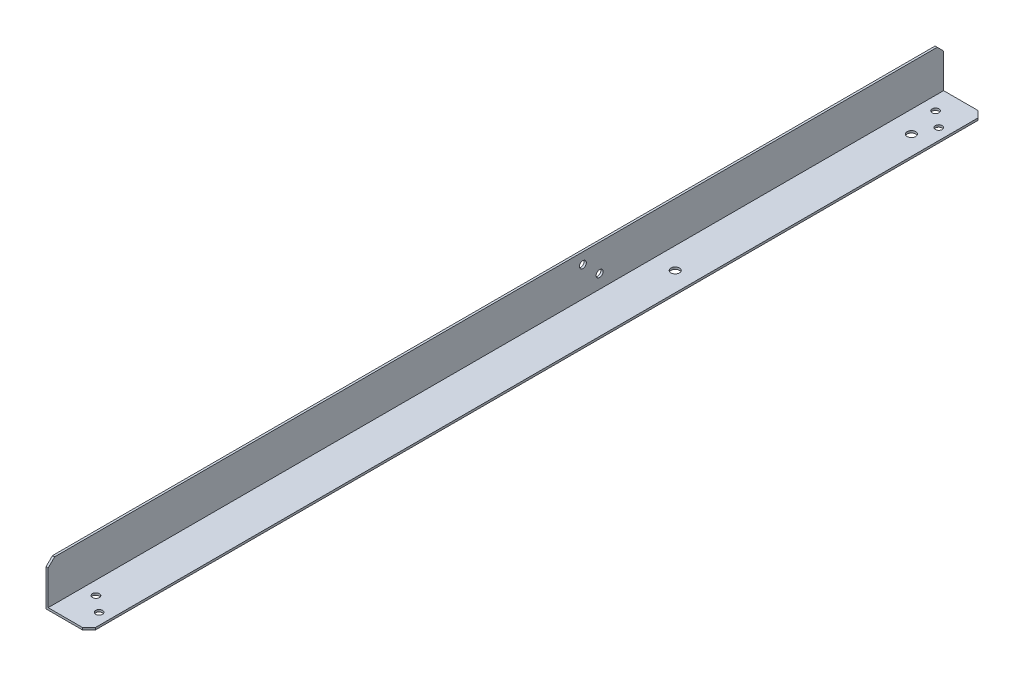
SolidWorks part; units mm, degrees
material "6063-T5"
ref_plane "Спереди" through (0, 0, 0) normal (0, 0, 1) x (1, 0, 0)
ref_plane "Сверху" through (0, 0, 0) normal (0, 1, 0) x (1, 0, 0)
ref_plane "Справа" through (0, 0, 0) normal (1, 0, 0) x (0, 0, -1)
sketch "Sketch1" plane through (0, 0, 0) normal (0, 0, 1) x (1, 0, 0)
  line L0 (0, 0) -> (20, 0)
  line L1 (20, 0) -> (20, 1)
  line L2 (20, 1) -> (1, 1)
  line L3 (1, 1) -> (1, 20)
  line L4 (1, 20) -> (0, 20)
  line L5 (0, 20) -> (0, 0)
  dimension "D1" = 20
  dimension "D2" = 20
  dimension "D4" = 1
extrude "Base" add sketch "Sketch1" along normal blind 417
chamfer "Chamfer1" distance 3 angle 45 4 edges at (20, 0.5, 417) (0.5, 20, 417) (0.5, 20, 0) (20, 0.5, 0)
hole_wizard "Ø3.2 (3.2) Cable Carrier Holes" positions "Sketch6" profile "Sketch7" hole size "Ø3.2" standard "ANSI Metric" end condition through all
sketch "Sketch6" plane through (1, 0, 0) normal (1, 0, 0) x (0, 0, -1)
  line L0 (-414, 0) -> (-3, 0) construction
  line L1 (0, 1) -> (0, 17) construction
  point P0 (-168, 14.85)
  point P2 (-160.2, 7.35)
  dimension "D1" = 7.5
  dimension "D2" = 7.8
  dimension "D3" = 7.35
  dimension "D4" = 168
sketch "Sketch7" plane through (1, 14.85, 168) normal (0, 1, 0) x (0, 0, -1)
  line L0 (0, 0) -> (0, 1)
  line L1 (0, 1) -> (1.6, 1)
  line L2 (1.6, 1) -> (1.6, 0)
  line L5 (1.6, 0) -> (0, 0)
  line L11 (0, -6.35) -> (0, 107.95) construction
  dimension "Thru Hole Dia." = 3.2
  dimension "Thru Hole Depth" = 1
hole_wizard "Ø3.2 (3.2) Diameter Hole2" positions "Sketch8" profile "Sketch9" hole size "Ø3.2" standard "ANSI Metric" end condition through all
sketch "Sketch8" plane through (0, 1, 0) normal (0, 1, 0) x (1, 0, 0)
  line L0 (0, -414) -> (0, -3) construction
  line L2 (17, -417) -> (1, -417) construction
  point P0 (7.25, -401)
  point P2 (14.75, -407)
  point P4 (7.25, -10)
  point P6 (14.75, -16)
  point P9 (0, 0)
  point P10 (0, 0)
  dimension "D1" = 6
  dimension "D2" = 6
  dimension "D3" = 7.5
  dimension "D4" = 7.25
  dimension "D5" = 10
  dimension "D6" = 391
sketch "Sketch9" plane through (7.25, 1, 401) normal (1, 0, 0) x (0, 0, 1)
  line L0 (0, 0) -> (0, 1)
  line L1 (0, 1) -> (1.6, 1)
  line L2 (1.6, 1) -> (1.6, 0)
  line L5 (1.6, 0) -> (0, 0)
  line L11 (0, -6.35) -> (0, 107.95) construction
  dimension "Thru Hole Dia." = 3.2
  dimension "Thru Hole Depth" = 1
hole_wizard "Ø4.0 (4) Cable Tie Holes" positions "Sketch10" profile "Sketch11" hole size "Ø4.0" standard "ANSI Metric" end condition through all
sketch "Sketch10" plane through (0, 1, 0) normal (0, 1, 0) x (1, 0, 0)
  line L0 (0, -414) -> (0, -3) construction
  line L1 (17, 0) -> (1, 0) construction
  point P0 (11, -25)
  point P2 (11, -135)
  point P5 (0, 0)
  dimension "D1" = 11
  dimension "D2" = 25
  dimension "D3" = 135
sketch "Sketch11" plane through (11, 1, 25) normal (1, 0, 0) x (0, 0, 1)
  line L0 (0, 0) -> (0, 1)
  line L1 (0, 1) -> (2, 1)
  line L2 (2, 1) -> (2, 0)
  line L5 (2, 0) -> (0, 0)
  line L11 (0, -6.35) -> (0, 107.95) construction
  dimension "Thru Hole Dia." = 4
  dimension "Thru Hole Depth" = 1
equation "\"D1@Sketch1\"=\"D2@Sketch1\""
